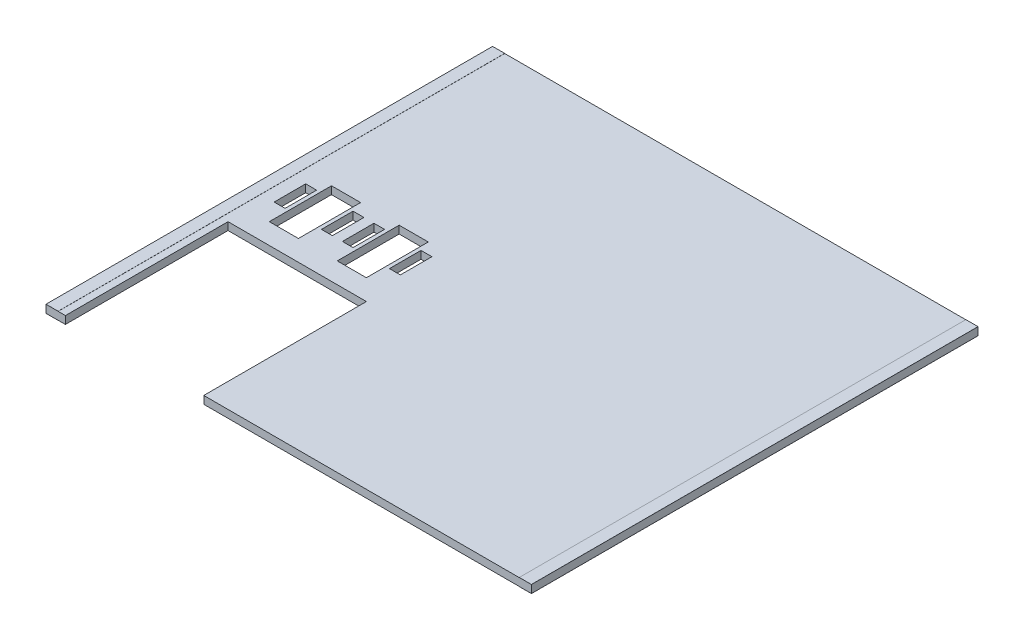
SolidWorks part; units mm, degrees
ref_plane "Front Plane" through (0, 0, 0) normal (0, 0, 1) x (1, 0, 0)
ref_plane "Top Plane" through (0, 0, 0) normal (0, 1, 0) x (1, 0, 0)
ref_plane "Right Plane" through (0, 0, 0) normal (1, 0, 0) x (0, 0, -1)
sketch "Sketch1" plane through (0, 0, 0) normal (0, 1, 0) x (1, 0, 0)
  line L0 (4, -11) -> (4, 81) construction
  line L1 (32.5, -11) -> (32.5, 81) construction
  line L2 (0, 22.5) -> (100, 22.5) construction
  line L3 (0, -11) -> (4, -11)
  line L4 (4, -11) -> (4, 22.5)
  line L5 (0, 81) -> (100, 81) construction
  line L6 (0, 81) -> (0, -11) construction
  line L7 (0, -11) -> (100, -11) construction
  line L8 (100, 81) -> (100, -11) construction
  line L9 (4, 22.5) -> (32.5, 22.5)
  line L10 (32.5, 22.5) -> (32.5, -11)
  line L11 (32.5, -11) -> (100, -11)
  line L12 (100, -11) -> (100, 81)
  line L13 (100, 81) -> (0, 81)
  line L14 (0, 81) -> (0, -11)
extrude "Boss-Extrude1" add sketch "Sketch1" along normal blind 1.5875
sketch "Sketch3" plane through (0, 1.5875, 0) normal (0, 1, 0) x (1, 0, 0)
  line L0 (0, -11) -> (4, -11) construction
  line L1 (0, 81) -> (2.5, 81)
  line L2 (0, 81) -> (0, -11)
  line L3 (0, -11) -> (2.5, -11)
  line L4 (2.5, 81) -> (2.5, -11)
  line L5 (32.5, -11) -> (100, -11) construction
  line L6 (100, 81) -> (97.5, 81)
  line L7 (100, 81) -> (100, -11)
  line L8 (100, -11) -> (97.5, -11)
  line L9 (97.5, 81) -> (97.5, -11)
extrude "Boss-Extrude2" add sketch "Sketch3" along normal blind 0.025 separate body
sketch "Sketch5" plane through (0, 0, 0) normal (0, -1, 0) x (1, 0, 0)
  line L0 (100, -81) -> (0, -81) construction
  line L1 (0, 11) -> (2.5, 11)
  line L2 (0, 11) -> (0, -81)
  line L3 (0, -81) -> (2.5, -81)
  line L4 (2.5, 11) -> (2.5, -81)
  line L6 (100, 11) -> (97.5, 11)
  line L7 (100, 11) -> (100, -81)
  line L8 (100, -81) -> (97.5, -81)
  line L9 (97.5, 11) -> (97.5, -81)
extrude "Boss-Extrude3" add sketch "Sketch5" along normal blind 0.025 separate body
ref_plane "center-of-slot" through (0, 0.7937, 0) normal (0, -1, 0) x (-1, 0, 0)
sketch "Sketch6" plane through (0, 1.5875, 0) normal (0, 1, 0) x (1, 0, 0)
  line L0 (22.25, 26.75) -> (28.25, 26.75)
  line L1 (8.25, 26.75) -> (14.25, 26.75)
  line L2 (8.25, 26.75) -> (8.25, 39.5625)
  line L3 (8.25, 39.5625) -> (14.25, 39.5625)
  line L4 (14.25, 26.75) -> (14.25, 39.5625)
  line L5 (22.25, 26.75) -> (22.25, 39.5)
  line L6 (22.25, 39.5) -> (28.25, 39.5)
  line L7 (28.25, 26.75) -> (28.25, 39.5)
  line L8 (15, 37.25) -> (17.25, 37.25)
  line L9 (5.25, 37.25) -> (7.5, 37.25)
  line L10 (5.25, 37.25) -> (5.25, 30.75)
  line L11 (5.25, 30.75) -> (7.5, 30.75)
  line L12 (7.5, 37.25) -> (7.5, 30.75)
  line L13 (15, 37.25) -> (15, 30.75)
  line L14 (15, 30.75) -> (17.25, 30.75)
  line L15 (17.25, 37.25) -> (17.25, 30.75)
  line L16 (19.3125, 37.25) -> (21.5, 37.25)
  line L17 (19.3125, 37.25) -> (19.3125, 30.75)
  line L18 (19.3125, 30.75) -> (21.5, 30.75)
  line L19 (21.5, 37.25) -> (21.5, 30.75)
  line L20 (29, 37.25) -> (31.25, 37.25)
  line L21 (29, 37.25) -> (29, 30.75)
  line L22 (29, 30.75) -> (31.25, 30.75)
  line L23 (31.25, 37.25) -> (31.25, 30.75)
extrude "Cut-Extrude1" cut sketch "Sketch6" against normal through all
